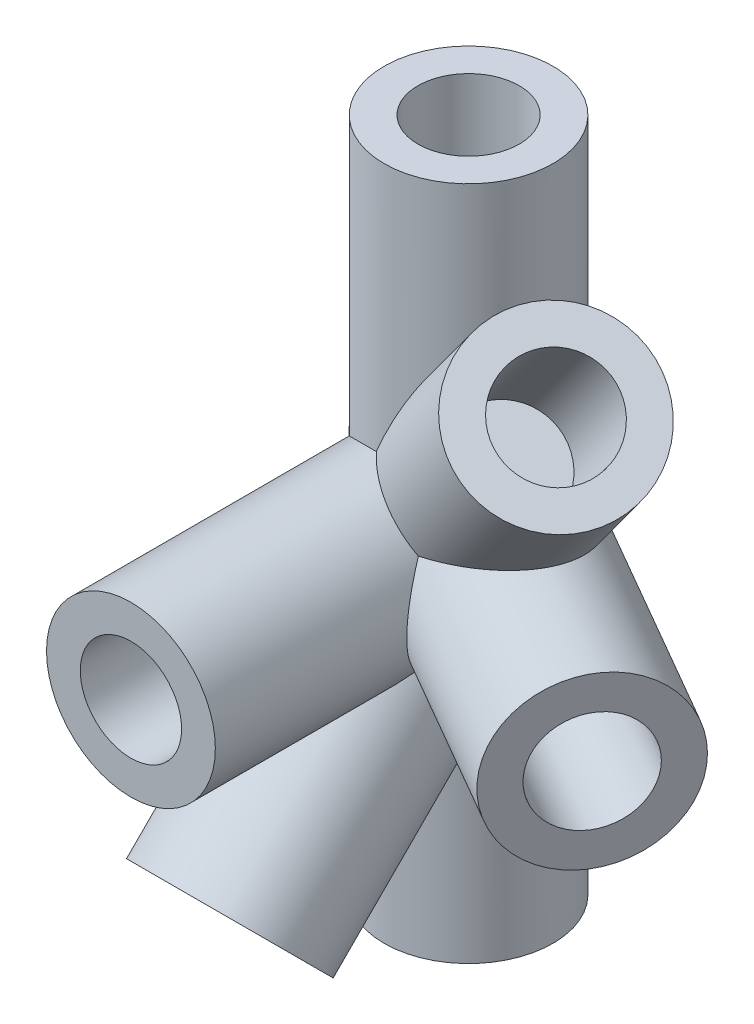
SolidWorks part; units mm, degrees
ref_plane "Front Plane" through (0, 0, 0) normal (0, 0, 1) x (1, 0, 0)
ref_plane "Top Plane" through (0, 0, 0) normal (0, 1, 0) x (1, 0, 0)
ref_plane "Right Plane" through (0, 0, 0) normal (1, 0, 0) x (0, 0, -1)
sketch "Sketch1" plane through (0, 0, 0) normal (0, 1, 0) x (1, 0, 0)
  circle A1 centre (0, 0) radius 5
  dimension "D1" = 10
extrude "Boss-Extrude1" add sketch "Sketch1" along normal blind 40 contours A1
sketch "Sketch2" plane through (0, 0, 0) normal (0, 0, 1) x (1, 0, 0)
  line L0 (-5, 0) -> (5, 0) construction
  circle A0 centre (0, 20) radius 5
  dimension "D1" = 10
  dimension "D2" = 10
  dimension "D3" = 20
extrude "Boss-Extrude2" add sketch "Sketch2" along normal blind 20 contours A0
sketch "Sketch3" plane through (0, 0, 0) normal (1, 0, 0) x (0, 0, -1)
  line L0 (0, 20) -> (8.7519, 11.2481) construction
  line L1 (-5, 25) -> (0, 20) construction
ref_plane "Plane1" through (0, 10, -10) normal (0, -0.7071, 0.7071) x (-1, 0, 0)
sketch "Sketch4" plane through (0, 10, -10) normal (0, -0.7071, 0.7071) x (-1, 0, 0)
  line L0 (5, -14.1421) -> (-5, -14.1421) construction
  circle A0 centre (0, -14.1421) radius 5
  dimension "D1" = 10
extrude "Boss-Extrude3" add sketch "Sketch4" along normal blind 20 contours A0
sketch "Sketch5" plane through (0, 0, 0) normal (0, 1, 0) x (1, 0, 0)
  line L0 (0, 0) -> (11.9747, -6.9136) construction
  line L1 (0, 0) -> (0, -20) construction
  line L2 (-5, -20) -> (5, -20) construction
  line L3 (0, 0) -> (-6.524, 3.7666) construction
  line L4 (11.9747, -6.9136) -> (8.6669, -12.643) construction
  dimension "D1" = 60
ref_plane "Plane2" through (11.9747, 0, 6.9136) normal (0.866, 0, 0.5) x (0.5, 0, -0.866)
sketch "Sketch6" plane through (11.9747, 0, 6.9136) normal (0.866, 0, 0.5) x (0.5, 0, -0.866)
  line L0 (9.9689, 20) -> (-8.8605, 20) construction
  circle A0 centre (0, 20) radius 5
  dimension "D1" = 10
extrude "Boss-Extrude4" add sketch "Sketch6" against normal up to vertex (13.8272 mm away) and the other way blind 10 contours A0 up to point (0, 0, 0)
ref_plane "Plane3" through (0, 0, 0) normal (-0.5, 0, 0.866) x (0.866, 0, 0.5)
sketch "Sketch7" plane through (0, 0, 0) normal (-0.5, 0, 0.866) x (0.866, 0, 0.5)
  line L0 (0, 0) -> (20, 0) construction
  dimension "D1" = 20
sketch "Sketch8" plane through (20.635, 0, 11.9136) normal (0.866, 0, 0.5) x (0.5, 0, -0.866)
  circle A0 centre (0, 20) radius 5
  circle A1 centre (0, 20) radius 5 construction
extrude "Cut-Extrude1" cut sketch "Sketch8" against normal up to vertex (3.8272 mm away) contours A0 up to point (17.3205, 0, 10)
sketch "Sketch12" plane through (0, 0, 0) normal (-0.5, 0, 0.866) x (0.866, 0, 0.5)
  line L0 (0, 20) -> (16.3502, 36.3502) construction
  line L1 (0, 20) -> (-4.376, 11.2481) construction
  line L2 (0, 20) -> (19.6256, 20) construction
  dimension "D1" = 45
ref_plane "Plane4" through (8.6603, 10, 5) normal (0.6124, 0.7071, 0.3536) x (0.7906, -0.5477, -0.2739)
sketch "Sketch13" plane through (8.6603, 10, 5) normal (0.6124, 0.7071, 0.3536) x (0.7906, -0.5477, -0.2739)
  circle A0 centre (-10.9545, 8.9443) radius 5
  dimension "D1" = 10
extrude "Boss-Extrude5" add sketch "Sketch13" along normal blind 20 contours A0
sketch "Sketch14" plane through (0, 40, 0) normal (0, 1, 0) x (1, 0, 0)
  circle A0 centre (0, 0) radius 3
  dimension "D1" = 6
extrude "Cut-Extrude2" cut sketch "Sketch14" against normal blind 12 contours A0
sketch "Sketch15" plane through (0, 0, 0) normal (0, -1, 0) x (1, 0, 0)
  circle A0 centre (0, 0) radius 3
  dimension "D1" = 6
extrude "Cut-Extrude3" cut sketch "Sketch15" against normal blind 12 contours A0
sketch "Sketch16" plane through (0, -4.1421, 4.1421) normal (0, -0.7071, 0.7071) x (1, 0, 0)
  circle A0 centre (0, 14.1421) radius 3
  circle A1 centre (0, 14.1421) radius 5 construction
  dimension "D1" = 6
extrude "Cut-Extrude4" cut sketch "Sketch16" against normal blind 12
sketch "Sketch17" plane through (0, 0, 20) normal (0, 0, 1) x (1, 0, 0)
  circle A0 centre (0, 20) radius 3
  circle A1 centre (0, 20) radius 5 construction
  dimension "D1" = 6
extrude "Cut-Extrude5" cut sketch "Sketch17" against normal blind 12
sketch "Sketch18" plane through (17.3205, 0, 10) normal (0.866, 0, 0.5) x (0.5, 0, -0.866)
  circle A0 centre (0, 20) radius 3
  circle A1 centre (0, 20) radius 5 construction
  dimension "D1" = 6
extrude "Cut-Extrude6" cut sketch "Sketch18" against normal blind 12 contours A0
sketch "Sketch19" plane through (20.9077, 24.1421, 12.0711) normal (0.6124, 0.7071, 0.3536) x (0.7906, -0.5477, -0.2739)
  circle A0 centre (-10.9545, 8.9443) radius 3
  circle A1 centre (-10.9545, 8.9443) radius 5 construction
  dimension "D1" = 6
extrude "Cut-Extrude7" cut sketch "Sketch19" against normal blind 12
